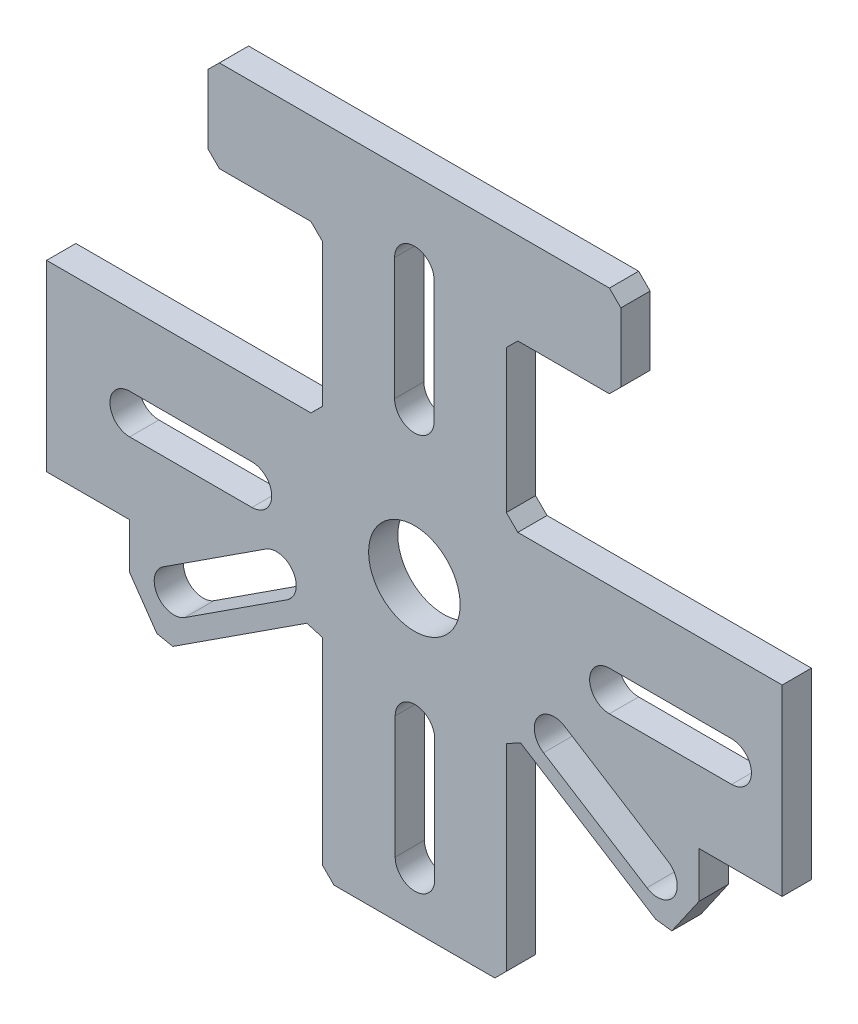
SolidWorks part; units mm, degrees
ref_plane "Front" through (0, 0, 0) normal (0, 0, 1) x (1, 0, 0)
ref_plane "Top" through (0, 0, 0) normal (0, 1, 0) x (1, 0, 0)
ref_plane "Right" through (0, 0, 0) normal (1, 0, 0) x (0, 0, -1)
sketch "Sketch1" plane through (0, 0, 0) normal (0, 0, 1) x (1, 0, 0)
  line L0 (-21.21, 37.9525) -> (21.21, 37.9525)
  line L2 (22.46, 36.7075) -> (22.46, 29.2375)
  line L6 (10, 11.205) -> (11.25, 9.96)
  line L7 (11.25, 9.96) -> (40, 9.96)
  line L8 (40, 9.96) -> (40, -9.96)
  line L9 (40, -9.96) -> (30.9636, -9.96)
  line L10 (30.9636, -9.96) -> (30.9636, -14.9312)
  line L11 (30.9636, -14.9312) -> (28, -19.2042)
  line L13 (11.545, -9.7101) -> (10, -10.5619)
  line L14 (10, -10.5619) -> (10, -32.0177)
  line L15 (10, -32.0177) -> (8.75, -33.2627)
  line L16 (8.75, -33.2627) -> (-8.75, -33.2627)
  line L17 (-8.75, -33.2627) -> (-10, -32.0177)
  line L18 (-10, -32.0177) -> (-10, -10.5619)
  line L19 (-10, -10.5619) -> (-11.6936, -10.0676)
  line L21 (-28, -19.2042) -> (-30.9636, -14.9312)
  line L22 (-30.9636, -14.9312) -> (-30.9636, -9.96)
  line L23 (-30.9636, -9.96) -> (-40, -9.96)
  line L24 (-40, -9.96) -> (-40, 9.96)
  line L25 (-40, 9.96) -> (-11.25, 9.96)
  line L26 (-11.25, 9.96) -> (-10, 11.205)
  line L29 (-21.21, 27.9925) -> (-22.46, 29.2375)
  line L30 (-22.46, 29.2375) -> (-22.46, 36.7075)
  line L31 (-22.46, 36.7075) -> (-21.21, 37.9525)
  line L32 (-26.2688, -19.5438) -> (-11.6936, -10.0676)
  line L33 (-26.2688, -19.5438) -> (-28, -19.2042)
  line L34 (28, -19.2042) -> (26.2495, -18.9843)
  line L35 (26.2495, -18.9843) -> (11.545, -9.7101)
  line L36 (22.46, 36.7075) -> (21.21, 37.9525)
  line L37 (21.21, 27.9925) -> (22.46, 29.2375)
  line L38 (-21.21, 27.9925) -> (-11.25, 27.9925)
  line L39 (-11.25, 27.9925) -> (-10, 26.7475)
  line L40 (21.21, 27.9925) -> (11.25, 27.9925)
  line L41 (11.25, 27.9925) -> (10, 26.7475)
  line L42 (-10, 11.205) -> (-10, 26.7475)
  line L43 (10, 11.205) -> (10, 26.7475)
  line L44 (0, 29.1498) -> (0, 15.8544) construction
  line L45 (2.15, 29.1498) -> (2.15, 15.8544)
  line L46 (-2.15, 29.1498) -> (-2.15, 15.8544)
  line L47 (0.0617, -13.9952) -> (0.0617, -27.2906) construction
  line L48 (2.2117, -13.9952) -> (2.2117, -27.2906)
  line L49 (-2.0883, -13.9952) -> (-2.0883, -27.2906)
  line L50 (21.21, 0) -> (34.5054, 0) construction
  line L55 (21.21, 2.15) -> (34.5054, 2.15)
  line L56 (21.21, -2.15) -> (34.5054, -2.15)
  line L57 (-30.9636, 0) -> (-17.6682, 0) construction
  line L58 (-30.9636, 2.15) -> (-17.6682, 2.15)
  line L59 (-30.9636, -2.15) -> (-17.6682, -2.15)
  line L60 (-26.1466, -14.3711) -> (-15, -7.1241) construction
  line L61 (-27.3185, -12.5686) -> (-16.1719, -5.3216)
  line L62 (-24.9747, -16.1737) -> (-13.8281, -8.9266)
  line L63 (15.1942, -7.5788) -> (26.4397, -14.6713) construction
  line L64 (16.3412, -5.7602) -> (27.5867, -12.8528)
  line L65 (14.0473, -9.3973) -> (25.2928, -16.4899)
  circle A0 centre (0, 0) radius 4.98
  arc A1 (2.15, 29.1498) -> (-2.15, 29.1498) centre (0, 29.1498) ccw
  arc A2 (-2.15, 15.8544) -> (2.15, 15.8544) centre (0, 15.8544) ccw
  arc A3 (2.2117, -13.9952) -> (-2.0883, -13.9952) centre (0.0617, -13.9952) ccw
  arc A4 (-2.0883, -27.2906) -> (2.2117, -27.2906) centre (0.0617, -27.2906) ccw
  arc A9 (21.21, 2.15) -> (21.21, -2.15) centre (21.21, 0) ccw
  arc A10 (34.5054, -2.15) -> (34.5054, 2.15) centre (34.5054, 0) ccw
  arc A11 (-30.9636, 2.15) -> (-30.9636, -2.15) centre (-30.9636, 0) ccw
  arc A12 (-17.6682, -2.15) -> (-17.6682, 2.15) centre (-17.6682, 0) ccw
  arc A13 (-27.3185, -12.5686) -> (-24.9747, -16.1737) centre (-26.1466, -14.3711) ccw
  arc A14 (-13.8281, -8.9266) -> (-16.1719, -5.3216) centre (-15, -7.1241) ccw
  arc A15 (16.3412, -5.7602) -> (14.0473, -9.3973) centre (15.1942, -7.5788) ccw
  arc A16 (25.2928, -16.4899) -> (27.5867, -12.8528) centre (26.4397, -14.6713) ccw
  point P9 (16.23, 27.9925)
  point P31 (0, 22.5021)
  point P44 (0.0617, -20.6429)
  point P53 (27.8577, 0)
  point P61 (-24.3159, 0)
  point P66 (-20.5733, -10.7476)
  point P75 (20.817, -11.125)
  dimension "D1" = 9.96
  dimension "D2" = 80
  dimension "D3" = 40
  dimension "D4" = 9.96
  dimension "D5" = 9.96
  dimension "D6" = 28
  dimension "D7" = 28
  dimension "D8" = 44.92
  dimension "D9" = 22.46
  dimension "D10" = 1.245
  dimension "D11" = 7.47
  dimension "D12" = 1.25
  dimension "D13" = 1.25
  dimension "D14" = 1.25
  dimension "D15" = 1.25
  dimension "D16" = 20
  dimension "D17" = 20
  dimension "D18" = 4.3
  dimension "D19" = 9.96
extrude "Boss-Extrude1" add sketch "Sketch1" along normal blind 3.18
